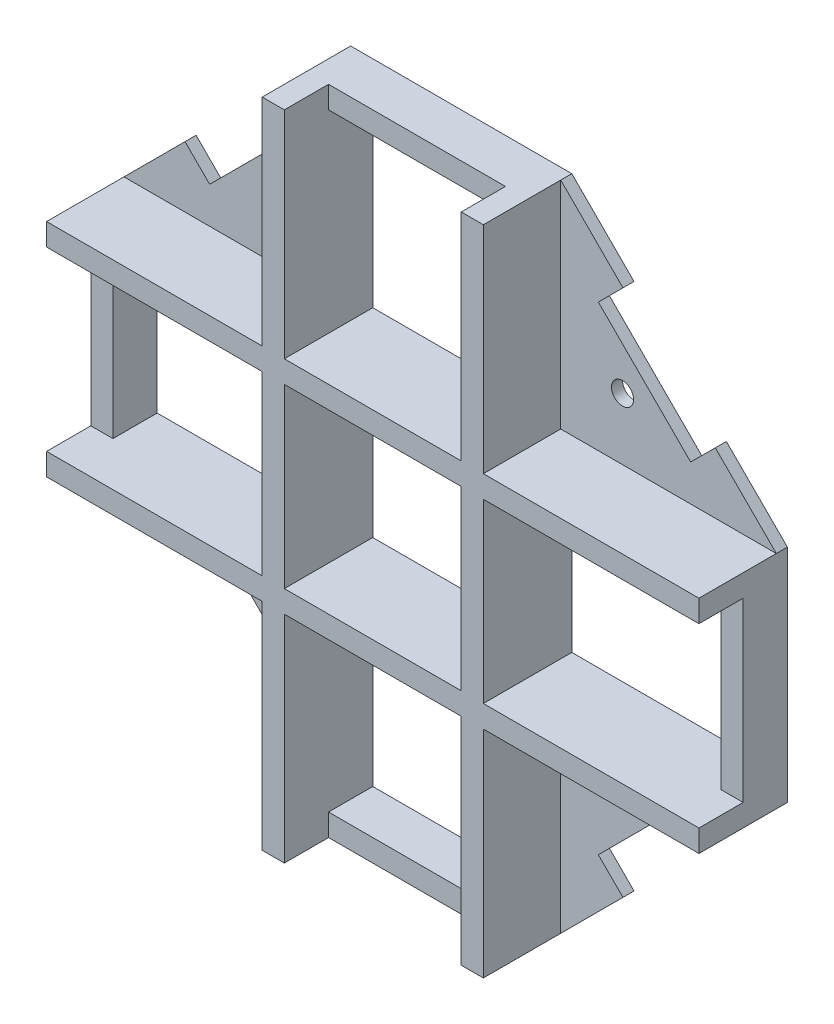
SolidWorks part; units mm, degrees
material "6061-T6 (SS)"
ref_plane "Front Plane" through (0, 0, 0) normal (0, 0, 1) x (1, 0, 0)
ref_plane "Top Plane" through (0, 0, 0) normal (0, 1, 0) x (1, 0, 0)
ref_plane "Right Plane" through (0, 0, 0) normal (1, 0, 0) x (0, 0, -1)
sketch "Sketch1" plane through (0, 0, 0) normal (0, 0, 1) x (1, 0, 0)
  line L1 (12.7, -37.465) -> (-12.7, -37.465)
  line L2 (12.7, -37.465) -> (12.7, 37.465)
  line L3 (12.7, 37.465) -> (-12.7, 37.465)
  line L4 (-12.7, -37.465) -> (-12.7, 37.465)
  line L5 (12.7, -37.465) -> (-12.7, 37.465) construction
  line L6 (12.7, 37.465) -> (-12.7, -37.465) construction
  line L7 (37.465, -12.7) -> (-37.465, -12.7)
  line L8 (37.465, -12.7) -> (37.465, 12.7)
  line L9 (37.465, 12.7) -> (-37.465, 12.7)
  line L10 (-37.465, -12.7) -> (-37.465, 12.7)
  line L11 (37.465, -12.7) -> (-37.465, 12.7) construction
  line L12 (37.465, 12.7) -> (-37.465, -12.7) construction
  point P0 (0, 0)
  point P6 (0, 0)
  dimension "D1" = 74.93
  dimension "D2" = 25.4
  dimension "D3" = 25.4
  dimension "D4" = 74.93
extrude "Boss-Extrude1" add sketch "Sketch1" along normal blind 10.16 contours L10 L7 L4 L9 | L2 L9 L4 L7 | L9 L2 L3 L4 | L8 L9 L2 L7 | L2 L7 L4 L1 region at (0, -25.0825, 0) region at (0, 0, 0) region at (25.0825, 0, 0) region at (-25.0825, 0, 0) region at (0, 25.0825, 0)
sketch "Sketch2" plane through (0, 0, 10.16) normal (0, 0, 1) x (1, 0, 0)
  line L0 (0, 0) -> (0, 16.4382) construction
  line L1 (10.16, -10.16) -> (-10.16, -10.16)
  line L2 (10.16, -10.16) -> (10.16, 10.16)
  line L3 (10.16, 10.16) -> (-10.16, 10.16)
  line L4 (-10.16, -10.16) -> (-10.16, 10.16)
  line L5 (10.16, -10.16) -> (-10.16, 10.16) construction
  line L6 (10.16, 10.16) -> (-10.16, -10.16) construction
  line L7 (10.16, 12.7) -> (-10.16, 12.7)
  line L8 (10.16, 12.7) -> (10.16, 34.925)
  line L9 (10.16, 34.925) -> (-10.16, 34.925)
  line L10 (-10.16, 12.7) -> (-10.16, 34.925)
  line L11 (10.16, 12.7) -> (-10.16, 34.925) construction
  line L12 (10.16, 34.925) -> (-10.16, 12.7) construction
  line L13 (0, 0) -> (-32.0898, 0) construction
  line L14 (10.16, -34.925) -> (-10.16, -34.925)
  line L15 (-10.16, -12.7) -> (-10.16, -34.925)
  line L16 (10.16, -12.7) -> (-10.16, -12.7)
  line L17 (10.16, -12.7) -> (10.16, -34.925)
  line L18 (-34.925, 10.16) -> (-12.7, 10.16)
  line L19 (34.925, -10.16) -> (12.7, -10.16)
  line L20 (34.925, -10.16) -> (34.925, 10.16)
  line L21 (34.925, 10.16) -> (12.7, 10.16)
  line L22 (12.7, -10.16) -> (12.7, 10.16)
  line L23 (34.925, -10.16) -> (12.7, 10.16) construction
  line L24 (34.925, 10.16) -> (12.7, -10.16) construction
  line L25 (-12.7, -10.16) -> (-12.7, 10.16)
  line L26 (-34.925, -10.16) -> (-12.7, -10.16)
  line L27 (-34.925, -10.16) -> (-34.925, 10.16)
  point P0 (0, 0)
  point P6 (0, 23.8125)
  point P20 (23.8125, 0)
  dimension "D1" = 20.32
  dimension "D2" = 20.32
  dimension "D3" = 22.225
  dimension "D4" = 2.54
  dimension "D5" = 20.32
  dimension "D6" = 22.225
  dimension "D7" = 20.32
  dimension "D8" = 2.54
extrude "Cut-Extrude1" cut sketch "Sketch2" against normal blind 10.16
sketch "Sketch4" plane through (0, 0, 10.16) normal (0, 0, 1) x (1, 0, 0)
  line L0 (12.7, 37.465) -> (-12.7, 37.465) construction
  line L1 (10.16, 34.925) -> (-10.16, 34.925)
  line L2 (10.16, 34.925) -> (10.16, 37.465)
  line L3 (10.16, 37.465) -> (-10.16, 37.465)
  line L4 (-10.16, 34.925) -> (-10.16, 37.465)
  line L5 (10.16, 12.7) -> (10.16, 34.925) construction
  line L6 (-10.16, 34.925) -> (-10.16, 12.7) construction
  line L12 (37.465, -12.7) -> (37.465, 12.7) construction
  line L13 (34.925, 10.16) -> (37.465, 10.16)
  line L14 (34.925, 10.16) -> (34.925, -10.16)
  line L15 (34.925, -10.16) -> (37.465, -10.16)
  line L16 (37.465, 10.16) -> (37.465, -10.16)
  line L17 (12.7, -10.16) -> (34.925, -10.16) construction
  line L18 (34.925, 10.16) -> (12.7, 10.16) construction
  line L19 (0, 0) -> (17.8539, 0) construction
  line L20 (0, 0) -> (0, -24.0674) construction
  line L21 (-34.925, -10.16) -> (-37.465, -10.16)
  line L22 (-34.925, 10.16) -> (-37.465, 10.16)
  line L23 (-34.925, 10.16) -> (-34.925, -10.16)
  line L24 (-37.465, 10.16) -> (-37.465, -10.16)
  line L25 (10.16, -37.465) -> (-10.16, -37.465)
  line L26 (-10.16, -34.925) -> (-10.16, -37.465)
  line L27 (10.16, -34.925) -> (-10.16, -34.925)
  line L28 (10.16, -34.925) -> (10.16, -37.465)
extrude "Cut-Extrude2" cut sketch "Sketch4" against normal blind 5.08
sketch "Sketch5" plane through (0, 0, 0) normal (0, 0, 1) x (1, 0, 0)
  line L0 (-37.465, 12.7) -> (-12.7, 37.465)
  line L1 (-12.7, 37.465) -> (-12.7, 12.7)
  line L2 (-12.7, 12.7) -> (-37.465, 12.7)
  line L3 (12.7, 37.465) -> (37.465, 12.7)
  line L4 (37.465, 12.7) -> (12.7, 12.7)
  line L5 (12.7, 12.7) -> (12.7, 37.465)
  line L6 (0, 0) -> (7.2753, 7.2753) construction
  line L7 (0, 0) -> (-12.7, 12.7) construction
  line L8 (37.465, -12.7) -> (12.7, -12.7)
  line L9 (12.7, -37.465) -> (37.465, -12.7)
  line L10 (12.7, -12.7) -> (12.7, -37.465)
  line L11 (-12.7, -37.465) -> (-12.7, -12.7)
  line L12 (-37.465, -12.7) -> (-12.7, -37.465)
  line L13 (-12.7, -12.7) -> (-37.465, -12.7)
extrude "Boss-Extrude2" add sketch "Sketch5" along normal blind 1.27
sketch "Sketch6" plane through (0, 0, 1.27) normal (0, 0, 1) x (1, 0, 0)
  line L0 (0, 0) -> (-10.16, 10.16) construction
  line L1 (0, 0) -> (10.16, 10.16) construction
  circle A0 centre (-19.799, 19.799) radius 1.27
  circle A1 centre (19.799, 19.799) radius 1.27
  circle A2 centre (19.799, -19.799) radius 1.27
  circle A3 centre (-19.799, -19.799) radius 1.27
  dimension "D1" = 28
  dimension "D2" = 2.54
  dimension "D4" = 2.54
  dimension "D3" = 28
extrude "Cut-Extrude3" cut sketch "Sketch6" against normal blind 1.27
sketch "Sketch9" plane through (0, 0, 1.27) normal (0, 0, 1) x (1, 0, 0)
  line L0 (-30.455, 19.71) -> (-27.6266, 16.8816)
  line L1 (-12.7, 37.465) -> (-37.465, 12.7) construction
  line L2 (-27.6266, 16.8816) -> (-17.02, 27.4882)
  line L3 (-17.02, 27.4882) -> (-19.8484, 30.3166)
  line L4 (-19.8484, 30.3166) -> (-30.455, 19.71)
  line L5 (-12.7, 12.7) -> (-25.1517, 25.0133) construction
  line L6 (0, 37.465) -> (0, -37.465) construction
  line L7 (10.16, 37.465) -> (-10.16, 37.465) construction
  line L8 (-10.16, -37.465) -> (10.16, -37.465) construction
  line L9 (-37.465, 0) -> (37.465, 0) construction
  line L10 (-37.465, 10.16) -> (-37.465, -10.16) construction
  line L11 (37.465, -10.16) -> (37.465, 10.16) construction
  line L12 (-17.02, -27.4882) -> (-19.8484, -30.3166)
  line L13 (-27.6266, -16.8816) -> (-17.02, -27.4882)
  line L14 (-30.455, -19.71) -> (-27.6266, -16.8816)
  line L15 (-19.8484, -30.3166) -> (-30.455, -19.71)
  line L16 (27.6266, -16.8816) -> (17.02, -27.4882)
  line L17 (30.455, -19.71) -> (27.6266, -16.8816)
  line L18 (19.8484, -30.3166) -> (30.455, -19.71)
  line L19 (17.02, -27.4882) -> (19.8484, -30.3166)
  line L20 (17.02, 27.4882) -> (19.8484, 30.3166)
  line L21 (27.6266, 16.8816) -> (17.02, 27.4882)
  line L22 (30.455, 19.71) -> (27.6266, 16.8816)
  line L23 (19.8484, 30.3166) -> (30.455, 19.71)
  dimension "D1" = 15
  dimension "D2" = 4
  dimension "D3" = 90.32
extrude "Cut-Extrude4" cut sketch "Sketch9" against normal up to surface (1.27 mm away) contours L4 L0 L2 L3 | L12 L15 L14 L13 | L16 L19 L18 L17 | L20 L23 L22 L21 up to face at (-21.069, -19.799, 0)
